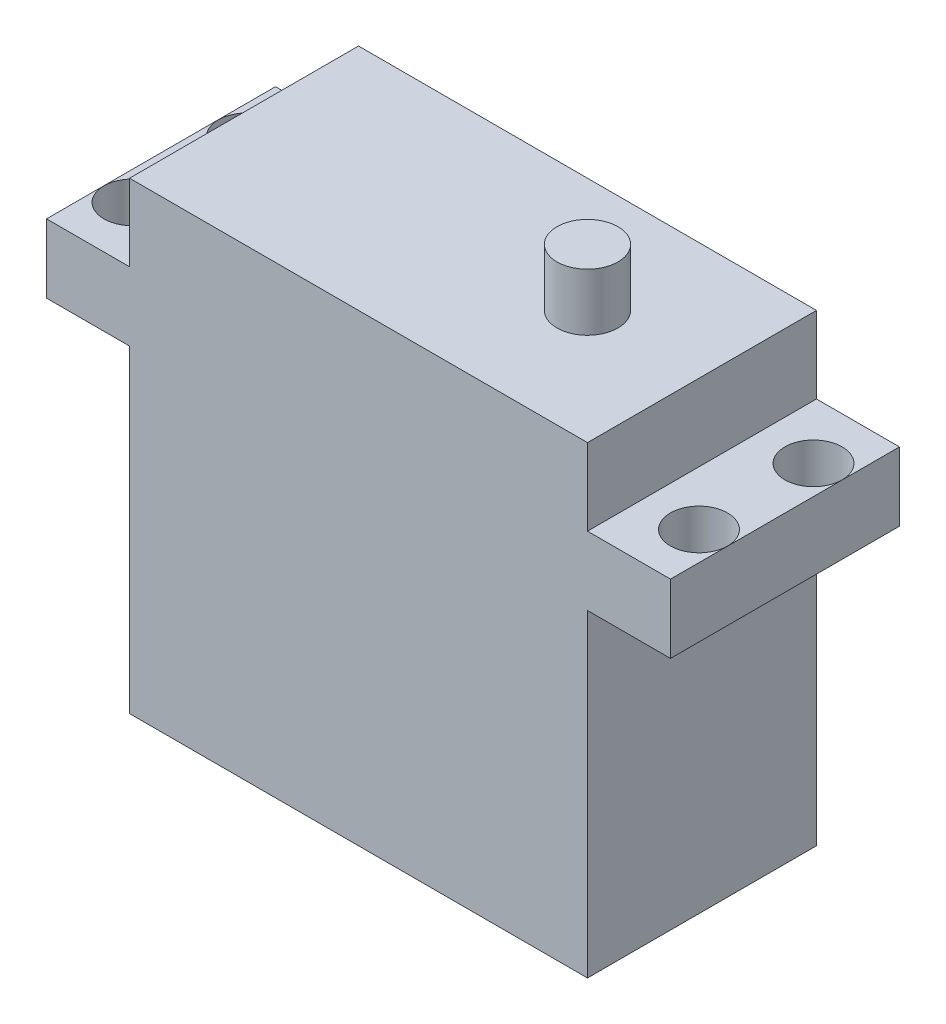
SolidWorks part; units mm, degrees
ref_plane "Front Plane" through (0, 0, 0) normal (0, 0, 1) x (1, 0, 0)
ref_plane "Top Plane" through (0, 0, 0) normal (0, 1, 0) x (1, 0, 0)
ref_plane "Right Plane" through (0, 0, 0) normal (1, 0, 0) x (0, 0, -1)
sketch "Sketch2" plane through (0, 0, 0) normal (0, 1, 0) x (1, 0, 0)
  line L0 (-24.74, 10) -> (-24.74, -10) construction
  line L1 (-27.25, -10) -> (27.25, -10)
  line L2 (-27.25, -10) -> (-27.25, 10)
  line L3 (-27.25, 10) -> (27.25, 10)
  line L4 (27.25, -10) -> (27.25, 10)
  line L5 (-27.25, -10) -> (27.25, 10) construction
  line L6 (-27.25, 10) -> (27.25, -10) construction
  line L7 (-20, -10) -> (20, -10)
  line L8 (-20, -10) -> (-20, 10)
  line L9 (-20, 10) -> (20, 10)
  line L10 (20, -10) -> (20, 10)
  line L11 (-20, -10) -> (20, 10) construction
  line L12 (-20, 10) -> (20, -10) construction
  line L13 (24.74, -10) -> (24.74, 10) construction
  line L14 (-27.25, 5) -> (27.25, 5) construction
  line L15 (27.25, -5) -> (-27.25, -5) construction
  line L16 (0, 0) -> (10, 0) construction
  circle A4 centre (10, 0) radius 2.6652
  circle A5 centre (24.74, 5) radius 2.5
  circle A6 centre (24.74, -5) radius 2.5
  circle A7 centre (-24.74, 5) radius 2.5
  circle A8 centre (-24.74, -5) radius 2.5
  point P0 (0, 0)
  point P6 (0, 0)
  dimension "D1" = 54.5
  dimension "D2" = 20
  dimension "D3" = 40
  dimension "D4" = 2.51
  dimension "D5" = 2.51
  dimension "D6" = 10
  dimension "D7" = 5
  dimension "D8" = 10
extrude "Boss-Extrude1" add sketch "Sketch2" along normal blind 40.5 contours L1 L10 L3 L8 A4 | A4 region at (-0.287, 0, 0) region at (10, 0, 0)
extrude "Boss-Extrude3" add sketch "Sketch2<5>" along normal blind 6 from offset 27.8 contours L1 L8 L3 L2 A8 A7 | L10 L1 L4 L3 A6 A5 region at (-23.2109, 0, 0) region at (23.2109, 0, 0)
sketch "Sketch2<5>" plane through (0, 0, 0) normal (0, 1, 0) x (1, 0, 0) same geometry as "Sketch2"
extrude "Boss-Extrude4" add sketch "Sketch2<6>" along normal blind 45.5 contours A4 region at (10, 0, 0)
sketch "Sketch2<6>" plane through (0, 0, 0) normal (0, 1, 0) x (1, 0, 0) same geometry as "Sketch2"
